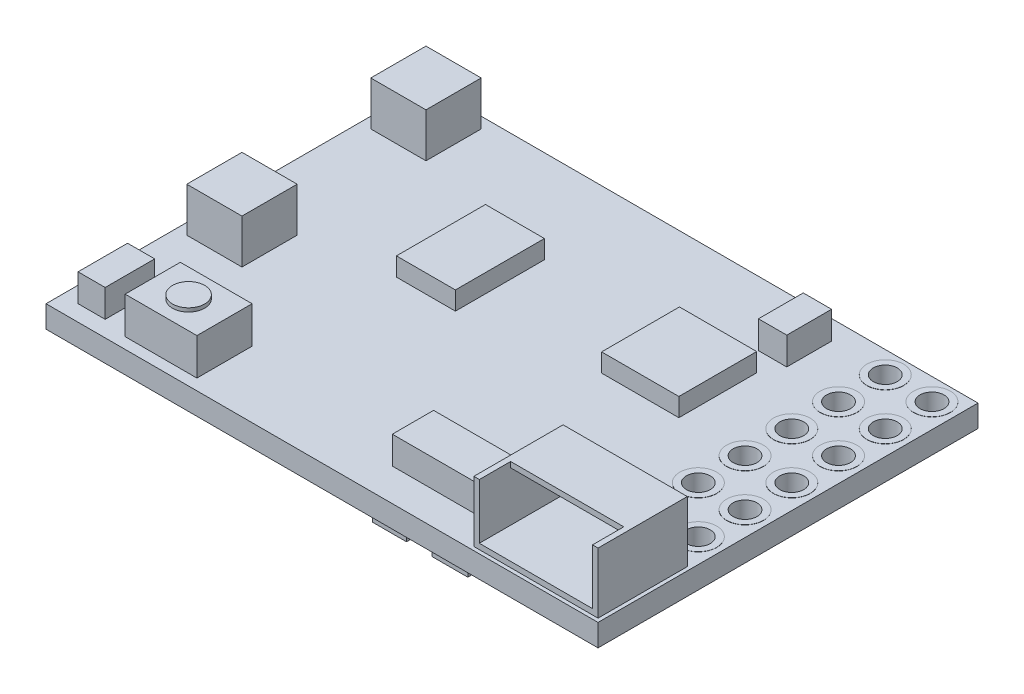
SolidWorks part; units mm, degrees
ref_plane "Front Plane" through (0, 0, 0) normal (0, 0, 1) x (1, 0, 0)
ref_plane "Top Plane" through (0, 0, 0) normal (0, 1, 0) x (1, 0, 0)
ref_plane "Right Plane" through (0, 0, 0) normal (1, 0, 0) x (0, 0, -1)
sketch "Sketch1" plane through (0, 0, 0) normal (0, 1, 0) x (1, 0, 0)
  line L1 (-15, 10.325) -> (15, 10.325)
  line L2 (-15, 10.325) -> (-15, -10.325)
  line L3 (-15, -10.325) -> (15, -10.325)
  line L4 (15, 10.325) -> (15, -10.325)
  line L5 (-15, 10.325) -> (15, -10.325) construction
  line L6 (-15, -10.325) -> (15, 10.325) construction
  point P0 (0, 0)
  dimension "D1" = 30
  dimension "D2" = 20.65
extrude "Boss-Extrude1" add sketch "Sketch1" along normal blind 1.2
sketch "Sketch2" plane through (0, 1.2, 0) normal (0, 1, 0) x (1, 0, 0)
  line L0 (13.7, 10.325) -> (13.7, -10.325) construction
  line L1 (15, 10.325) -> (-15, 10.325) construction
  line L2 (-15, -10.325) -> (15, -10.325) construction
  line L3 (11.16, 9.125) -> (13.7, 9.125) construction
  line L4 (15, -10.325) -> (15, 10.325) construction
  line L5 (13.7, 9.125) -> (13.7, 6.585) construction
  circle A0 centre (13.7, 9.125) radius 0.65
  circle A1 centre (11.16, 9.125) radius 0.65
  circle A2 centre (11.16, 6.585) radius 0.65
  circle A3 centre (11.16, 4.045) radius 0.65
  circle A4 centre (11.16, 1.505) radius 0.65
  circle A5 centre (11.16, -1.035) radius 0.65
  circle A6 centre (11.16, -3.575) radius 0.65
  circle A7 centre (13.7, 6.585) radius 0.65
  circle A8 centre (13.7, 4.045) radius 0.65
  circle A9 centre (13.7, 1.505) radius 0.65
  circle A10 centre (13.7, -1.035) radius 0.65
  circle A11 centre (13.7, -3.575) radius 0.65
  dimension "D3" = 1.3
  dimension "D1" = 1.3
  dimension "D2" = 2
  dimension "D4" = 1.2
  dimension "D6" = 2.54
  dimension "D5" = 6
extrude "Cut-Extrude1" cut sketch "Sketch2" against normal up to next
sketch "Sketch3" plane through (0, 1.2, 0) normal (0, 1, 0) x (1, 0, 0)
  line L0 (-15, -10.325) -> (15, -10.325) construction
  line L1 (14.8, -10.125) -> (8.05, -10.125)
  line L2 (14.8, -10.125) -> (14.8, -5.275)
  line L3 (14.8, -5.275) -> (8.05, -5.275)
  line L4 (8.05, -10.125) -> (8.05, -5.275)
  line L5 (15, -10.325) -> (15, 10.325) construction
  point P5 (14.6082, -9.9313)
  dimension "D1" = 6.75
  dimension "D2" = 4.85
  dimension "D3" = 0.2
  dimension "D4" = 0.2
extrude "Boss-Extrude2" add sketch "Sketch3" along normal blind 3.3
sketch "Sketch4" plane through (0, 1.2, 0) normal (0, 1, 0) x (1, 0, 0)
  line L0 (15, 10.325) -> (-15, 10.325) construction
  line L1 (-14.4, 9.725) -> (-11.4, 9.725)
  line L2 (-14.4, 9.725) -> (-14.4, 6.725)
  line L3 (-14.4, 6.725) -> (-11.4, 6.725)
  line L4 (-11.4, 9.725) -> (-11.4, 6.725)
  line L5 (-15, 10.325) -> (-15, -10.325) construction
  line L6 (-15, 3.225) -> (15, 3.225) construction
  line L7 (15, -10.325) -> (15, 10.325) construction
  line L8 (-14.4, -0.275) -> (-11.4, -0.275)
  line L9 (-11.4, -3.275) -> (-11.4, -0.275)
  line L10 (-14.4, -3.275) -> (-11.4, -3.275)
  line L11 (-14.4, -3.275) -> (-14.4, -0.275)
  dimension "D1" = 3
  dimension "D2" = 3
  dimension "D3" = 0.6
  dimension "D4" = 0.6
  dimension "D5" = 7
extrude "Boss-Extrude3" add sketch "Sketch4" along normal blind 2.4
sketch "Sketch5" plane through (0, 1.2, 0) normal (0, 1, 0) x (1, 0, 0)
  line L0 (-15, 10.325) -> (-15, -10.325) construction
  line L1 (-11.3, -9.725) -> (-7.4, -9.725)
  line L2 (-11.3, -9.725) -> (-11.3, -6.725)
  line L3 (-11.3, -6.725) -> (-7.4, -6.725)
  line L4 (-7.4, -9.725) -> (-7.4, -6.725)
  line L5 (-15, -10.325) -> (15, -10.325) construction
  dimension "D1" = 3.9
  dimension "D2" = 3
  dimension "D3" = 3.7
  dimension "D4" = 0.6
extrude "Boss-Extrude4" add sketch "Sketch5" along normal blind 2
sketch "Sketch6" plane through (0, 3.2, 0) normal (0, 1, 0) x (1, 0, 0)
  line L0 (-11.3, -8.225) -> (-7.4, -8.225) construction
  line L1 (-11.3, -6.725) -> (-11.3, -9.725) construction
  line L2 (-7.4, -9.725) -> (-7.4, -6.725) construction
  line L3 (-9.35, -6.725) -> (-9.35, -9.725) construction
  line L4 (-7.4, -6.725) -> (-11.3, -6.725) construction
  line L5 (-11.3, -9.725) -> (-7.4, -9.725) construction
  circle A0 centre (-9.35, -8.225) radius 0.875
  dimension "D1" = 1.75
extrude "Boss-Extrude5" add sketch "Sketch6" along normal blind 0.2
sketch "Sketch7" plane through (0, 4.5, 0) normal (0, 1, 0) x (1, 0, 0)
  line L0 (11.425, -5.275) -> (11.425, -10.125) construction
  line L1 (14.8, -5.275) -> (8.05, -5.275) construction
  line L2 (8.05, -10.125) -> (14.8, -10.125) construction
  line L3 (8.05, -10.125) -> (14.8, -10.125) construction
  line L4 (8.35, -10.125) -> (14.5, -10.125)
  line L5 (8.35, -10.125) -> (8.35, -8.425)
  line L6 (8.35, -8.425) -> (14.5, -8.425)
  line L7 (14.5, -10.125) -> (14.5, -8.425)
  line L8 (8.05, -5.275) -> (8.05, -10.125) construction
  point P12 (11.425, -8.425)
  dimension "D1" = 0.3
  dimension "D2" = 1.7
extrude "Cut-Extrude2" cut sketch "Sketch7" against normal offset from surface (3 mm away) 0.3 up to face at (11.16, 1.2, 4.225)
sketch "Sketch8" plane through (0, 0, 8.425) normal (0, 0, 1) x (1, 0, 0)
  line L0 (14.5, 1.5) -> (14.5, 4.5) construction
  line L1 (8.35, 1.5) -> (14.5, 1.5)
  line L2 (8.35, 1.5) -> (8.35, 4.2)
  line L3 (8.35, 4.2) -> (14.5, 4.2)
  line L4 (14.5, 1.5) -> (14.5, 4.2)
  line L5 (14.5, 4.5) -> (8.35, 4.5) construction
  dimension "D1" = 0.3
extrude "Cut-Extrude3" cut sketch "Sketch8" against normal offset from surface (2.85 mm away) 0.3 up to face at (11.425, 2.85, 5.275)
sketch "Sketch9" plane through (0, 1.2, 0) normal (0, 1, 0) x (1, 0, 0)
  line L1 (7.5622, 5.7357) -> (3.3645, 5.7357)
  line L2 (7.5622, 5.7357) -> (7.5622, 1.506)
  line L3 (7.5622, 1.506) -> (3.3645, 1.506)
  line L4 (3.3645, 5.7357) -> (3.3645, 1.506)
  line L5 (-6.7291, 5.2871) -> (-3.5248, 5.2871)
  line L6 (-6.7291, 5.2871) -> (-6.7291, 0.4486)
  line L7 (-6.7291, 0.4486) -> (-3.5248, 0.4486)
  line L8 (-3.5248, 5.2871) -> (-3.5248, 0.4486)
  point P8 (-3.5248, 0.4486)
extrude "Boss-Extrude6" add sketch "Sketch9" along normal blind 1
sketch "Sketch10" plane through (0, 1.2, 0) normal (0, 1, 0) x (1, 0, 0)
  line L1 (8.1069, 9.2605) -> (6.5689, 9.2605)
  line L2 (8.1069, 9.2605) -> (8.1069, 6.8252)
  line L3 (8.1069, 6.8252) -> (6.5689, 6.8252)
  line L4 (6.5689, 9.2605) -> (6.5689, 6.8252)
  line L5 (7.6904, -6.3125) -> (2.0508, -6.3125)
  line L6 (7.6904, -6.3125) -> (7.6904, -8.5556)
  line L7 (7.6904, -8.5556) -> (2.0508, -8.5556)
  line L8 (2.0508, -6.3125) -> (2.0508, -8.5556)
  line L9 (-14.1311, -6.7611) -> (-12.6571, -6.7611)
  line L10 (-14.1311, -6.7611) -> (-14.1311, -9.4528)
  line L11 (-14.1311, -9.4528) -> (-12.6571, -9.4528)
  line L12 (-12.6571, -6.7611) -> (-12.6571, -9.4528)
extrude "Boss-Extrude7" add sketch "Sketch10" along normal blind 1.5
sketch "Sketch11" plane through (0, 0, 0) normal (0, -1, 0) x (1, 0, 0)
  line L0 (-15, 10.325) -> (15, 10.325) construction
  line L1 (-5.67, 3.005) -> (1.18, 3.005)
  line L2 (-5.67, 3.005) -> (-5.67, -3.845)
  line L3 (-5.67, -3.845) -> (1.18, -3.845)
  line L4 (1.18, 3.005) -> (1.18, -3.845)
  line L5 (-15, -10.325) -> (-15, 10.325) construction
  line L7 (6.633, 9.0362) -> (4.6783, 9.0362)
  line L8 (6.633, 9.0362) -> (6.633, 6.1203)
  line L9 (6.633, 6.1203) -> (4.6783, 6.1203)
  line L10 (4.6783, 9.0362) -> (4.6783, 6.1203)
  line L11 (3.3005, 9.0362) -> (1.4419, 9.0362)
  line L12 (3.3005, 9.0362) -> (3.3005, 6.1203)
  line L13 (3.3005, 6.1203) -> (1.4419, 6.1203)
  line L14 (1.4419, 9.0362) -> (1.4419, 6.1203)
  line L15 (4.9667, 5.0628) -> (6.3125, 5.0628)
  line L16 (4.9667, 5.0628) -> (4.9667, 2.3071)
  line L17 (4.9667, 2.3071) -> (6.3125, 2.3071)
  line L18 (6.3125, 5.0628) -> (6.3125, 2.3071)
  line L19 (-14.8681, -4.3258) -> (-11.9521, -4.3258)
  line L20 (-14.8681, -4.3258) -> (-14.8681, -9.5168)
  line L21 (-14.8681, -9.5168) -> (-11.9521, -9.5168)
  line L22 (-11.9521, -4.3258) -> (-11.9521, -9.5168)
  line L23 (-12.593, 4.3258) -> (-10.35, 4.3258)
  line L24 (-12.593, 4.3258) -> (-12.593, 1.3779)
  line L25 (-12.593, 1.3779) -> (-10.35, 1.3779)
  line L26 (-10.35, 4.3258) -> (-10.35, 1.3779)
  line L27 (-9.7412, -6.6009) -> (-8.2351, -6.6009)
  line L28 (-9.7412, -6.6009) -> (-9.7412, -8.9401)
  line L29 (-9.7412, -8.9401) -> (-8.2351, -8.9401)
  line L30 (-8.2351, -6.6009) -> (-8.2351, -8.9401)
  dimension "D1" = 6.85
  dimension "D2" = 7.32
  dimension "D3" = 9.33
extrude "Boss-Extrude8" add sketch "Sketch11" along normal blind 1.5
sketch "Sketch12" plane through (0, 1.2, 0) normal (0, 1, 0) x (1, 0, 0)
  circle A0 centre (11.16, 9.125) radius 1
  circle A1 centre (13.7, 9.125) radius 1
  circle A2 centre (13.7, 6.585) radius 1
  circle A3 centre (11.16, 6.585) radius 1
  circle A4 centre (11.16, 4.045) radius 1
  circle A5 centre (13.7, 4.045) radius 1
  circle A6 centre (13.7, 1.505) radius 1
  circle A7 centre (11.16, 1.505) radius 1
  circle A8 centre (11.16, -1.035) radius 1
  circle A9 centre (11.16, -3.575) radius 1
  circle A10 centre (13.7, -3.575) radius 1
  circle A11 centre (13.7, -1.035) radius 1
  circle A12 centre (11.16, -3.575) radius 0.65 construction
  circle A13 centre (13.7, -3.575) radius 0.65 construction
  circle A14 centre (13.7, -1.035) radius 0.65 construction
  circle A15 centre (11.16, -1.035) radius 0.65 construction
  circle A16 centre (11.16, 1.505) radius 0.65 construction
  circle A17 centre (13.7, 1.505) radius 0.65 construction
  circle A18 centre (13.7, 4.045) radius 0.65 construction
  circle A19 centre (11.16, 4.045) radius 0.65 construction
  circle A20 centre (11.16, 6.585) radius 0.65 construction
  circle A21 centre (13.7, 6.585) radius 0.65 construction
  circle A22 centre (13.7, 9.125) radius 0.65 construction
  circle A23 centre (11.16, 9.125) radius 0.65 construction
  circle A24 centre (11.16, -3.575) radius 0.65
  circle A25 centre (13.7, -3.575) radius 0.65
  circle A26 centre (13.7, -1.035) radius 0.65
  circle A27 centre (11.16, -1.035) radius 0.65
  circle A28 centre (11.16, 1.505) radius 0.65
  circle A29 centre (13.7, 1.505) radius 0.65
  circle A30 centre (13.7, 4.045) radius 0.65
  circle A31 centre (11.16, 4.045) radius 0.65
  circle A32 centre (11.16, 6.585) radius 0.65
  circle A33 centre (13.7, 6.585) radius 0.65
  circle A34 centre (13.7, 9.125) radius 0.65
  circle A35 centre (11.16, 9.125) radius 0.65
  dimension "D1" = 2
extrude "Boss-Extrude9" add sketch "Sketch12" along normal blind 0.01
ref_plane "Plane1" through (0, 0.6, 0) normal (0, 1, 0) x (1, 0, 0)
mirror "Mirror1" about plane through (0, 0.6, 0) normal (0, 1, 0) of "Boss-Extrude9"
